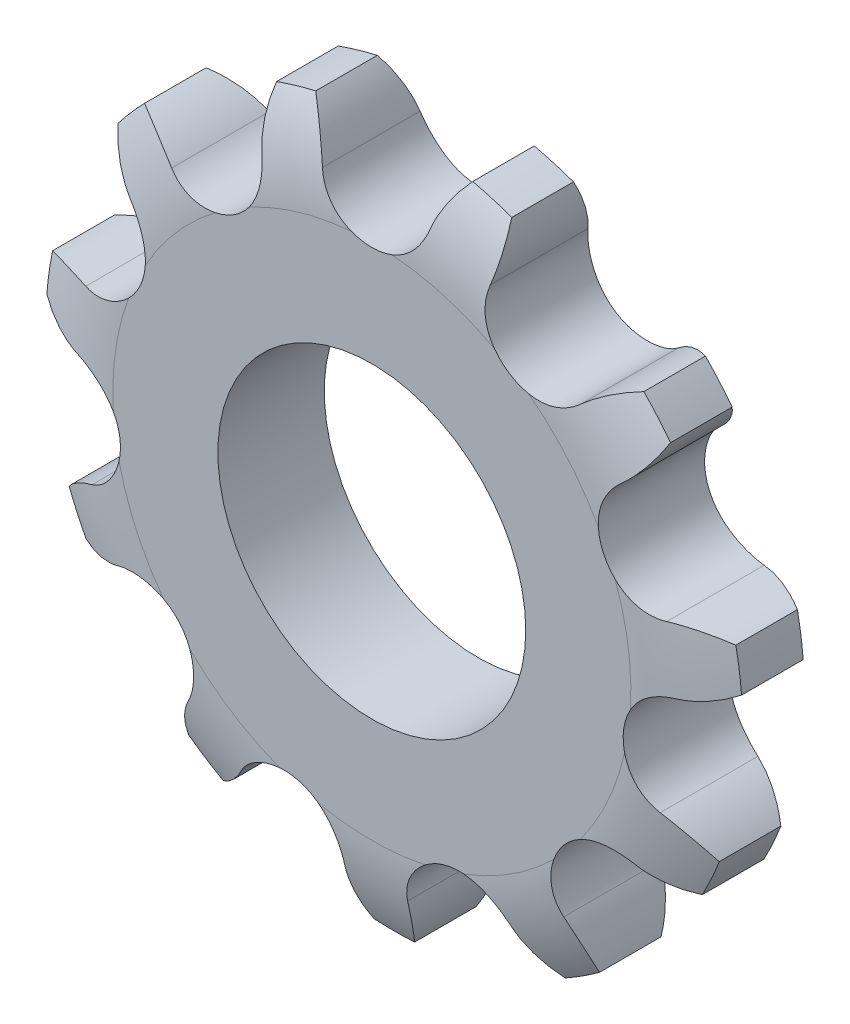
SolidWorks part; units mm, degrees
ref_plane "Mid plane" through (0, 0, 0) normal (0, 0, 1) x (1, 0, 0)
ref_plane "Top Plane" through (0, 0, 0) normal (0, 1, 0) x (1, 0, 0)
ref_plane "Right Plane" through (0, 0, 0) normal (1, 0, 0) x (0, 0, -1)
sketch "Sketch1" plane through (0, 0, 0) normal (0, 0, 1) x (1, 0, 0)
  circle A0 centre (0, 0) radius 31.6364
  dimension "Da" = 63.2728
extrude "Boss-Extrude1" add sketch "Sketch1" along normal mid plane 9.652 contours A0
sketch "Sketch2" plane through (0, 0, 0) normal (0, 1, 0) x (1, 0, 0)
  line L0 (-31.6364, -4.826) -> (31.6364, -4.826) construction
  line L1 (-31.6364, -4.826) -> (-23.5084, -4.826)
  line L2 (0, -4.826) -> (0, -98.6524) construction
  line L3 (-31.6364, -4.826) -> (-31.6364, -2.794)
  line L4 (-31.6364, 4.826) -> (-31.6364, -4.826) construction
  line L5 (0, -4.826) -> (31.6364, -4.826)
  arc A0 (-31.6364, -2.794) -> (-23.5084, -4.826) centre (-23.5084, 12.446) ccw
  dimension "h1" = 8.128
  dimension "r3" = 17.272
revolve "Cut-Revolve1" cut sketch "Sketch2" angle 360 about L2
mirror "Mirror1" about plane through (0, 0, 0) normal (0, 0, 1) of "Cut-Revolve1"
sketch "Sketch3" plane through (0, 0, 0) normal (0, 0, 1) x (1, 0, 0)
  line L0 (0, 0) -> (0, 239.6132) construction
  circle A0 centre (0, 0) radius 23.0939
  arc A2 (-7.1207, 30.8246) -> (-4.8742, 26.7427) centre (-15.232, 23.7014) cw
  circle A3 centre (0, 0) radius 31.6364 construction
  arc A4 (7.1207, 30.8246) -> (4.8742, 26.7427) centre (15.232, 23.7014) ccw
  arc A6 (7.1207, 30.8246) -> (-7.1207, 30.8246) centre (0, 0) ccw
  arc A8 (-4.8742, 26.7427) -> (4.8742, 26.7427) centre (0, 28.1739) ccw
  dimension "Dd" = 46.1878
  dimension "r2" = 5.08
  dimension "r1" = 10.795
  dimension "Dp1/2" = 28.1739
  dimension "Dp/2" = 28.1739
extrude "Cut-Extrude4" cut sketch "Sketch3" against normal mid plane 12.7 contours A6 A2 A8 A4
ref_axis "Axis1" through (0, 0, 0) along (0, 0, 1)
pattern_circular "CirPattern1" count 11 over 360 about axis through (0, 0, 0) along (0, 0, 1) of "Cut-Extrude4"
sketch "Sketch4" plane through (0, 0, 4.826) normal (0, 0, 1) x (1, 0, 0)
  circle A0 centre (0, 0) radius 45.72
  dimension "D1" = 91.44
extrude "Cut-Extrude5" [suppressed] cut sketch "Sketch4" against normal through all
sketch "Sketch5" [suppressed] plane through (0, 0, 4.826) normal (0, 0, 1) x (1, 0, 0)
  line L0 (0, 0) -> (0, 114.3) construction
  circle A0 centre (0, 0) radius 57.15 construction
  circle A1 centre (0, 57.15) radius 4.7625
  circle A2 centre (49.4934, 28.575) radius 4.7625
  circle A3 centre (49.4934, -28.575) radius 4.7625
  circle A4 centre (0, -57.15) radius 4.7625
  circle A5 centre (-49.4934, -28.575) radius 4.7625
  circle A6 centre (-49.4934, 28.575) radius 4.7625
  dimension "D1" = 114.3
  dimension "D2" = 9.525
  dimension "D3" = 6
extrude "Cut-Extrude6" [suppressed] cut sketch "Sketch5" against normal through all
sketch "Sketch6" [suppressed] plane through (0, 0, 4.826) normal (0, 0, 1) x (1, 0, 0)
  circle A0 centre (0, 0) radius 73.025 construction
  circle A1 centre (-73.025, 0) radius 15.875
  circle A2 centre (-36.5125, 63.2415) radius 15.875
  circle A3 centre (36.5125, 63.2415) radius 15.875
  circle A4 centre (73.025, 0) radius 15.875
  circle A5 centre (36.5125, -63.2415) radius 15.875
  circle A6 centre (-36.5125, -63.2415) radius 15.875
  dimension "D1" = 146.05
  dimension "D2" = 31.75
  dimension "D3" = 6
extrude "Cut-Extrude7" [suppressed] cut sketch "Sketch6" against normal through all
sketch "Chain OD" plane through (0, 0, 0) normal (0, 0, 1) x (1, 0, 0)
  circle A0 centre (0, 0) radius 35.5272
  dimension "D1" = 71.0544
sketch "Sketch7" plane through (0, 0, 4.826) normal (0, 0, 1) x (1, 0, 0)
  circle A0 centre (0, 0) radius 13.97
  dimension "D1" = 27.94
extrude "Cut-Extrude8" cut sketch "Sketch7" against normal through all
equation "\"Dp1/2@Sketch3\" = \"Dp/2@Sketch3\""
equation "\"D1@Chain OD\"=2*\"Dp1/2@Sketch3\"+.579"
